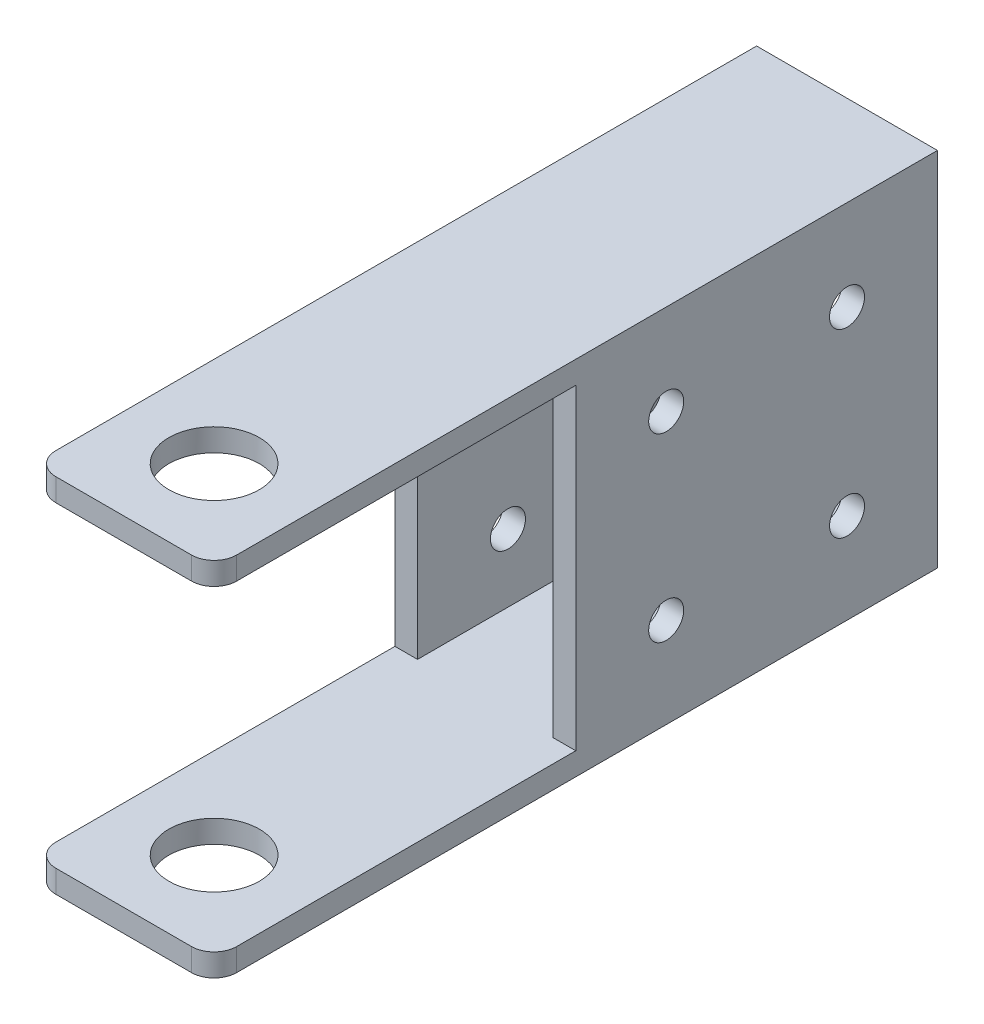
SolidWorks part; units mm, degrees
ref_plane "Front Plane" through (0, 0, 0) normal (0, 0, 1) x (1, 0, 0)
ref_plane "Top Plane" through (0, 0, 0) normal (0, 1, 0) x (1, 0, 0)
ref_plane "Right Plane" through (0, 0, 0) normal (1, 0, 0) x (0, 0, -1)
sketch "Sketch2" plane through (0, 0, 0) normal (0, 0, 1) x (1, 0, 0)
  line L1 (-12.7, 25.4) -> (12.7, 25.4)
  line L2 (-12.7, 25.4) -> (-12.7, -25.4)
  line L3 (-12.7, -25.4) -> (12.7, -25.4)
  line L4 (12.7, 25.4) -> (12.7, -25.4)
  line L5 (-12.7, 25.4) -> (12.7, -25.4) construction
  line L6 (-12.7, -25.4) -> (12.7, 25.4) construction
  point P0 (0, 0)
  dimension "D1" = 50.8
  dimension "D2" = 25.4
extrude "Boss-Extrude1" add sketch "Sketch2" along normal mid plane 101.6
sketch "Sketch3" plane through (12.7, 0, 0) normal (1, 0, 0) x (0, 0, -1)
  line L0 (0, 0) -> (-50.8, 0) construction
  line L1 (-50.8, -25.4) -> (-50.8, 25.4) construction
  line L2 (0, 22.225) -> (-50.8, 22.225)
  line L3 (0, -22.225) -> (-50.8, -22.225)
  line L4 (0, -22.225) -> (0, 22.225)
  line L5 (-50.8, -22.225) -> (-50.8, 22.225)
  dimension "D1" = 22.225
  dimension "D2" = 22.225
extrude "Cut-Extrude1" cut sketch "Sketch3" against normal through all
sketch "Sketch4" plane through (0, 25.4, 0) normal (0, 1, 0) x (1, 0, 0)
  line L0 (12.7, -50.8) -> (-12.7, -50.8) construction
  circle A0 centre (0, -38.1) radius 6.35
  dimension "D2" = 12.7
  dimension "D1" = 12.7
extrude "Cut-Extrude2" cut sketch "Sketch4" against normal through all
hole_wizard "#10 (0.1935) Diameter Hole2" positions "Sketch8" profile "Sketch7" hole size "#10" standard "ANSI Inch" end condition through all
sketch "Sketch8" plane through (12.7, 0, 0) normal (1, 0, 0) x (0, 0, -1)
  line L0 (12.7, 12.7) -> (38.1, 12.7) construction
  line L2 (0, 0) -> (50.8, 0) construction
  line L3 (50.8, -25.4) -> (50.8, 25.4) construction
  line L5 (-50.8, 25.4) -> (50.8, 25.4) construction
  point P0 (12.7, 12.7)
  point P2 (38.1, 12.7)
  point P4 (12.7, -12.7)
  point P6 (38.1, -12.7)
  dimension "D1" = 25.4
  dimension "D2" = 25.4
  dimension "D3" = 12.7
  dimension "D4" = 12.7
sketch "Sketch7" plane through (12.7, 12.7, -12.7) normal (0, 1, 0) x (0, 0, -1)
  line L0 (0, 0) -> (0, 25.4)
  line L1 (0, 25.4) -> (2.4574, 25.4)
  line L2 (2.4574, 25.4) -> (2.4574, 0)
  line L5 (2.4574, 0) -> (0, 0)
  line L11 (0, -6.35) -> (0, 107.95) construction
  dimension "Thru Hole Dia." = 4.9149
  dimension "Thru Hole Depth" = 25.4
sketch "Sketch9" plane through (0, 0, -50.8) normal (0, 0, -1) x (-1, 0, 0)
  line L8 (-9.525, 22.225) -> (-9.525, -22.225)
  line L9 (-9.525, -22.225) -> (9.525, -22.225)
  line L10 (9.525, -22.225) -> (9.525, 22.225)
  line L11 (9.525, 22.225) -> (-9.525, 22.225)
  line L12 (-9.525, 22.225) -> (-9.525, -22.225)
  line L13 (-9.525, -22.225) -> (9.525, -22.225)
  line L14 (9.525, -22.225) -> (9.525, 22.225)
  line L15 (9.525, 22.225) -> (-9.525, 22.225)
  dimension "D1" = 3.175
extrude "Cut-Extrude3" cut sketch "Sketch9" against normal through all
fillet "Fillet1" radius 3.175 4 edges at (-12.7, 23.8125, 50.8) (-12.7, -23.8125, 50.8) (12.7, 23.8125, 50.8) (12.7, -23.8125, 50.8)
